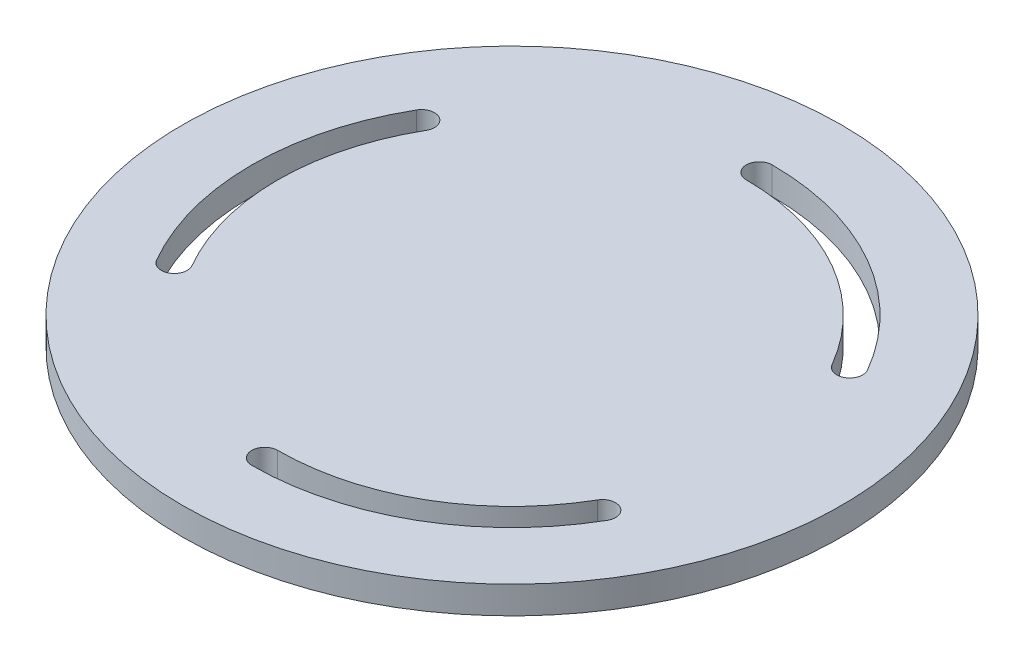
SolidWorks part; units mm, degrees
ref_plane "Front Plane" through (0, 0, 0) normal (0, 0, 1) x (1, 0, 0)
ref_plane "Top Plane" through (0, 0, 0) normal (0, 1, 0) x (1, 0, 0)
ref_plane "Right Plane" through (0, 0, 0) normal (1, 0, 0) x (0, 0, -1)
ref_axis "Axis2" through (0, 0, -88.99) along (0, 0, 1)
ref_axis "Axis1" through (0, -58.175, 0) along (0, 1, 0)
sketch "Sketch2" plane through (0, 0, 0) normal (0, 1, 0) x (1, 0, 0)
  circle A0 centre (0, 0) radius 76.1746
  arc A1 (0, 57.15) -> (49.4934, 28.575) centre (0, 0) cw construction
  arc A2 (52.0914, 30.075) -> (0, 60.15) centre (0, 0) ccw
  arc A3 (46.8953, 27.075) -> (0, 54.15) centre (0, 0) ccw
  arc A4 (46.8953, 27.075) -> (52.0914, 30.075) centre (49.4934, 28.575) ccw
  arc A5 (0, 60.15) -> (0, 54.15) centre (0, 57.15) ccw
  arc A6 (0, -54.15) -> (46.8953, -27.075) centre (0, 0) ccw
  arc A7 (0, -54.15) -> (0, -60.15) centre (0, -57.15) ccw
  arc A8 (52.0914, -30.075) -> (46.8953, -27.075) centre (49.4934, -28.575) ccw
  arc A9 (0, -60.15) -> (52.0914, -30.075) centre (0, 0) ccw
  arc A10 (49.4934, -28.575) -> (0, -57.15) centre (0, 0) cw construction
  arc A11 (-46.8953, 27.075) -> (-46.8953, -27.075) centre (0, 0) ccw
  arc A12 (-46.8953, 27.075) -> (-52.0914, 30.075) centre (-49.4934, 28.575) ccw
  arc A13 (-52.0914, -30.075) -> (-46.8953, -27.075) centre (-49.4934, -28.575) ccw
  arc A14 (-52.0914, 30.075) -> (-52.0914, -30.075) centre (0, 0) ccw
  arc A15 (-49.4934, -28.575) -> (-49.4934, 28.575) centre (0, 0) cw construction
  point P5 (28.575, 49.4934)
  point P11 (0, 38.1)
  point P14 (28.575, -49.4934)
  point P21 (-57.15, 0)
  point P26 (0, 0)
  dimension "D1" = 152.3492
  dimension "D2" = 57.15
  dimension "D3" = 6
  dimension "D6" = 38.1
  dimension "D4" = 60
  dimension "D5" = 3
extrude "Boss-Extrude1" add sketch "Sketch2" against normal blind 6.35
sketch "Sketch3" plane through (0, -6.35, 0) normal (0, -1, 0) x (1, 0, 0)
  point P0 (0, -38.1)
  point P2 (-36.8018, -9.861)
  dimension "D1" = 38.1
  dimension "D2" = 75
sketch3d "3DSketch1"
  line L0 (0, 0, 0) -> (0, 0, -38.1) construction
  line L1 (0, -6.35, 0) -> (-36.8018, -6.35, -9.861) construction
  line L2 (0, -58.175, 0) -> (0, 51.825, 0) construction
  line L6 (-31.7307, -6.35, -8.5022) -> (-41.8729, -6.35, -11.2198)
  line L7 (-41.8729, -6.35, -11.2198) -> (-41.8729, -10.35, -11.2198)
  line L10 (0, 0, -32.85) -> (0, -4, -32.85)
  line L11 (0, -4, -32.85) -> (0, -4, -43.35)
  line L12 (0, -4, -43.35) -> (0, 0, -43.35)
  line L13 (0, 0, -43.35) -> (0, 0, -32.85)
  line L14 (-41.8729, -10.35, -11.2198) -> (-31.7307, -10.35, -8.5022)
  line L15 (-31.7307, -10.35, -8.5022) -> (-31.7307, -6.35, -8.5022)
  arc A0 (0, 0, -38.1) -> (-36.8018, -6.35, -9.861) centre (0, -3.175, 0) cw
  point P0 (0, 0, -38.1)
  point P8 (-4.1137, 34.7038, 3.1566)
  dimension "D2" = 4
  dimension "D1" = 10.5
equation "\"Bodytube_ID\" = 5.998in"
equation "\"AB_Coupling_Screw_Diameter\"= 0.1065in"
equation "\"D1@Sketch2\"=\"Bodytube_ID\""
equation "\"Slot_Angle\"= 60deg"
equation "\"Slot_Width\"= 6mm"
equation "\"Slot_Radius\"= 2.25in"
equation "\"D2@Sketch2\"=\"Slot_Radius\""
equation "\"D4@Sketch2\"=\"Slot_Angle\""
equation "\"D3@Sketch2\"=\"Slot_Width\""
equation "\"Ramp_Slot_Radius\"= 1.5in"
equation "\"Screwhead_Clearance\"= 10.5mm"
equation "\"Hgt\"= 0.25in"
equation "\"D1@Boss-Extrude1\"=\"Hgt\""
equation "\"D6@Sketch2\"=\"Ramp_Slot_Radius\""
equation "\"Arc_Angle\"= 75"
equation "\"D1@Sketch3\"=\"Ramp_Slot_Radius\""
equation "\"D2@Sketch3\"=\"Arc_Angle\""
equation "\"Verticle_Head_Clearance\"= 4mm"
equation "\"D2@3DSketch1\"=\"Verticle_Head_Clearance\""
equation "\"D1@3DSketch1\"=\"Screwhead_Clearance\""
